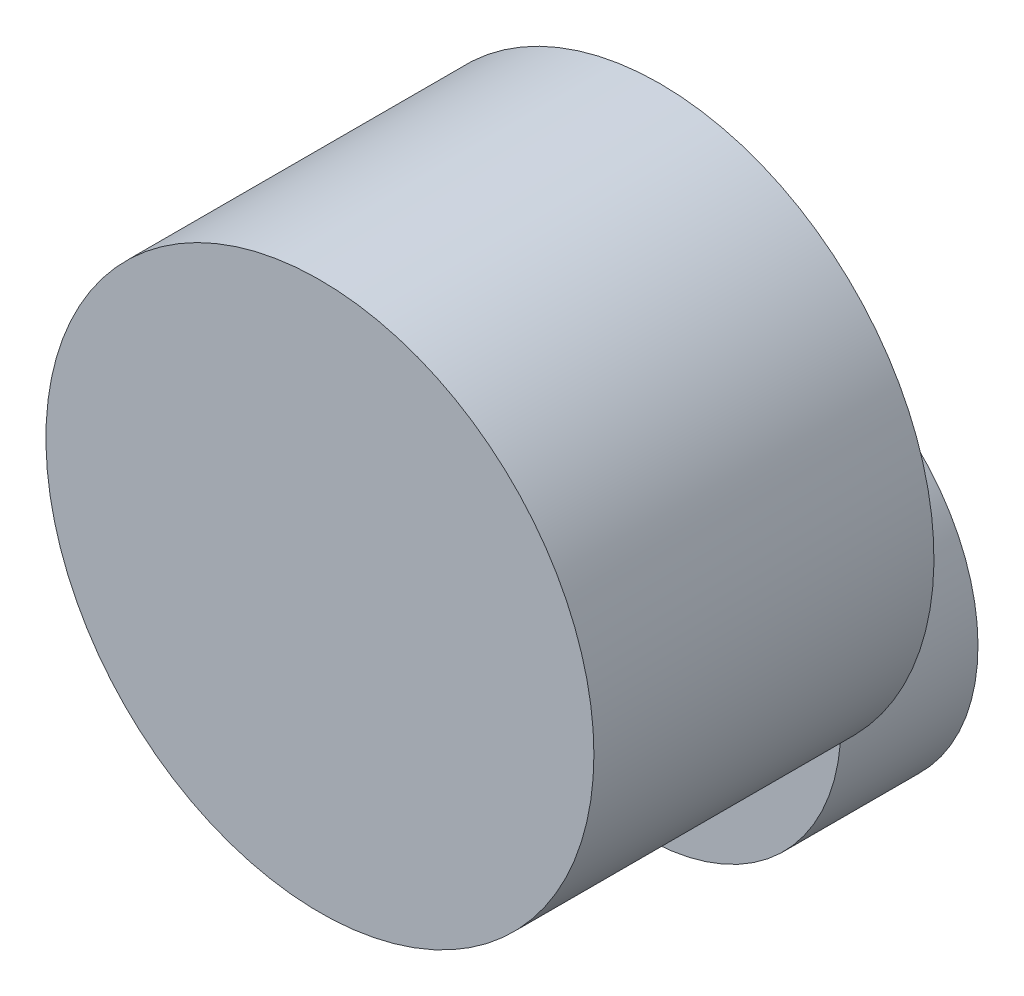
SolidWorks part; units mm, degrees
ref_plane "Front" through (0, 0, 0) normal (0, 0, 1) x (1, 0, 0)
ref_plane "Top" through (0, 0, 0) normal (0, 1, 0) x (1, 0, 0)
ref_plane "Right" through (0, 0, 0) normal (1, 0, 0) x (0, 0, -1)
sketch "Sketch1" plane through (0, 0, 0) normal (0, 0, 1) x (1, 0, 0)
  circle A0 centre (0, 0) radius 56
  dimension "D1" = 112
extrude "Extrude1" add sketch "Sketch1" along normal blind 69.5
sketch "Sketch2" plane through (0, 0, 0) normal (0, 0, -1) x (-1, 0, 0)
  line L0 (0, 0) -> (0, -36) construction
  circle A0 centre (0, -36) radius 40
  dimension "D1" = 80
  dimension "D2" = 36
extrude "Extrude2" add sketch "Sketch2" along normal blind 25 and the other way blind 3
sketch "Sketch3" plane through (0, 0, 0) normal (0, 0, -1) x (-1, 0, 0)
  circle A0 centre (0, 0) radius 49 construction
  circle A1 centre (-49, 0) radius 2.5
  circle A2 centre (0, 49) radius 2.5
  circle A3 centre (49, 0) radius 2.5
  dimension "D1" = 5
  dimension "D2" = 98
extrude "Cut-Extrude1" cut sketch "Sketch3" against normal blind 10
sketch "Sketch4" plane through (0, 0, -25) normal (0, 0, -1) x (-1, 0, 0)
  circle A0 centre (0, -36) radius 6.35
  circle A1 centre (0, -36) radius 40 construction
  dimension "D1" = 12.7
extrude "Extrude3" add sketch "Sketch4" along normal blind 12.7
ref_plane "cg_plane" through (0, 0, 31.75) normal (0, 0, -1) x (-1, 0, 0)
ref_axis "Axis1" through (0, 0, 69.5) along (0, 0, -1)
ref_plane "Plane1" through (0, 0, 0) normal (-0.5736, 0.8192, 0) x (-0.8192, -0.5736, 0)
